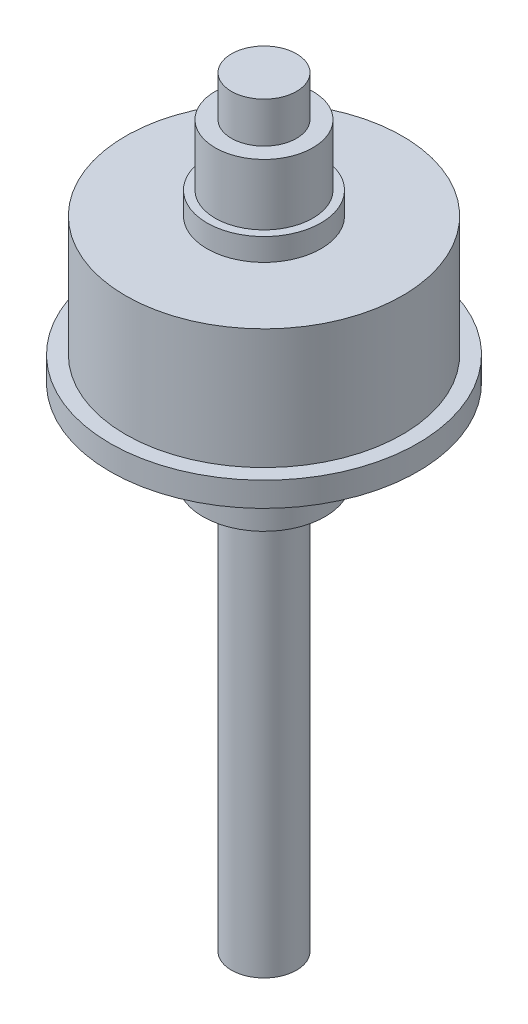
SolidWorks part; units mm, degrees
material "AISI 1035 Steel (SS)"
ref_plane "Front Plane" through (0, 0, 0) normal (0, 0, 1) x (1, 0, 0)
ref_plane "Top Plane" through (0, 0, 0) normal (0, 1, 0) x (1, 0, 0)
ref_plane "Right Plane" through (0, 0, 0) normal (1, 0, 0) x (0, 0, -1)
sketch "Sketch2" plane through (0, 0, 0) normal (0, 0, 1) x (1, 0, 0)
  line L0 (0, 40.0334) -> (0, -27.2464) construction
  line L11 (0, 0) -> (-4, 0)
  line L12 (-4, 0) -> (-4, -5)
  line L13 (-4, -5) -> (-6, -5)
  line L14 (-6, -5) -> (-6, -12.5)
  line L15 (-6, -12.5) -> (-7, -12.5)
  line L16 (-7, -12.5) -> (-7, -15.25)
  line L17 (-7, -15.25) -> (-17, -15.25)
  line L18 (-17, -15.25) -> (-17, -30.01)
  line L26 (0, -93.51) -> (0, 0)
  line L28 (-18.9, -33.01) -> (-18.9, -30.01)
  line L29 (-18.9, -30.01) -> (-17, -30.01)
  line L30 (-18.9, -33.01) -> (-9, -33.01)
  line L31 (-9, -33.01) -> (-9, -35.51)
  line L32 (-17, -30.01) -> (-17, -33.01) construction
  line L33 (-9, -35.51) -> (-7.5, -35.51)
  line L34 (-7.5, -35.51) -> (-7.5, -43.51)
  line L35 (-7.5, -43.51) -> (-4, -43.51)
  line L36 (-4, -43.51) -> (-4, -93.51)
  line L37 (-4, -93.51) -> (0, -93.51)
  dimension "D1" = 4
  dimension "D2" = 5
  dimension "D3" = 6
  dimension "D4" = 7.5
  dimension "D5" = 7
  dimension "D6" = 2.75
  dimension "D7" = 17
  dimension "D8" = 14.76
  dimension "D10" = 3
  dimension "D11" = 9
  dimension "D12" = 2.5
  dimension "D13" = 7.5
  dimension "D14" = 8
  dimension "D15" = 4
  dimension "D16" = 50
  dimension "D9" = 1.9
revolve "Revolve1" add sketch "Sketch2" angle 360 about L0
equation "\"Stator_OD\"= 68'No Tolerance given"
equation "\"A\"=18.34 'taken off spec sheet for 06808 (A)"
equation "\"Rotor_ID\"= 34'No Tolerance Given"
equation "\"back_bearing_Thickness\"= 8'randomish, thinnest off mcmaster"
equation "\"back_bearing_OD\"= 25'currently non-sense"
equation "\"Stator_Gap\"= 0.0375'+- 0.0125 (From 1.3.3.1 Kollmorgen manual)"
equation "\"Back_mount_hole\"= 1.75'To be tapped to M2 (USE LOCKTITE)"
equation "\"facePlate_Mount_Hole\"= 5.75'To be tapped to M6"
equation "\"final_shaftD\"= 8'NEMA 23 shaft diameter. Should fit with harmonic?"
equation "\"back_bearing_ID\"= 15'Random number"
equation "\"rotor_shaftD\"= \"Rotor_ID\" - (0.0185)*2'+-0.0065 (from manual)"
equation "\"back_bearing_IDOD\"= 18'Random number, OD of the inner bearing ring"
equation "\"final_shaftL\"= 50'random length. Idk"
equation "\"D1@Sketch2\" = \"final_shaftD\" / 2"
equation "\"D3@Sketch2\"=\"front_bearing_ID\"/2"
equation "\"D4@Sketch2\" = \"front_bearing_Thickness\" + 2.5"
equation "\"D5@Sketch2\"=\"front_bearing_IDOD\" / 2"
equation "\"D8@Sketch2\"=\"rotor_height\""
equation "\"front_bearing_ID\"= 12'random"
equation "\"front_bearing_OD\"= 20'random"
equation "\"front_bearing_IDOD\"= 14'random"
equation "\"front_bearing_Thickness\"= 5'randomish, thinnest off mcmaster"
equation "\"rotor_thickness\"= 2.4'measured off CAD"
equation "\"rotor_height\"= 14.76'+-0.08 taken off spec sheet for 06808 (C)"
equation "\"D11@Sketch2\"=\"back_bearing_IDOD\"/2"
equation "\"D13@Sketch2\"=\"back_bearing_ID\"/2"
equation "\"D14@Sketch2\"=\"back_bearing_Thickness\""
equation "\"D15@Sketch2\"=\"final_shaftD\"/2"
equation "\"D16@Sketch2\"=\"final_shaftL\""
equation "\"D9@Sketch2\"=\"rotor_thickness\"-0.5"
